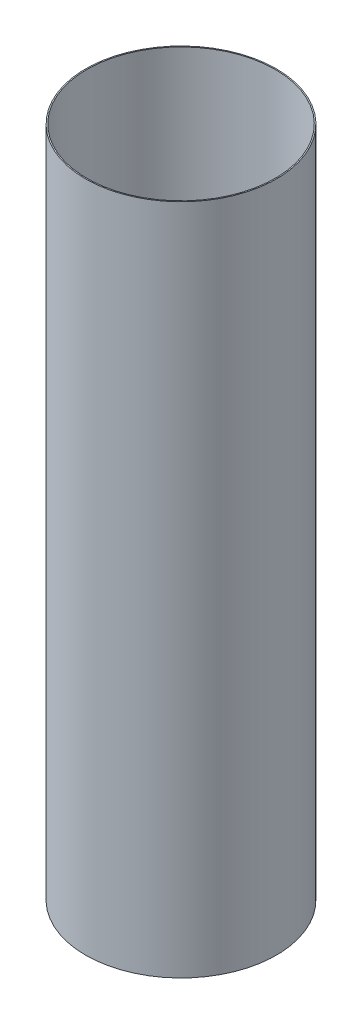
SolidWorks part; units mm, degrees
material "Hexcel AS4C (3000 Filaments)"
ref_plane "Front Plane" through (0, 0, 0) normal (0, 0, 1) x (1, 0, 0)
ref_plane "Top Plane" through (0, 0, 0) normal (0, 1, 0) x (1, 0, 0)
ref_plane "Right Plane" through (0, 0, 0) normal (1, 0, 0) x (0, 0, -1)
sketch "Sketch1" plane through (0, 0, 0) normal (0, 1, 0) x (1, 0, 0)
  circle A0 centre (0, 0) radius 83.439
  circle A1 centre (0, 0) radius 84.455
  dimension "D1" = 168.91
  dimension "D2" = 1.016
extrude "Boss-Extrude1" add sketch "Sketch1" along normal blind 595.0295
ref_plane "Plane1" through (0, 297.5148, 0) normal (0, 1, 0) x (1, 0, 0)
sketch "Sketch2" plane through (0, 0, 0) normal (0, 0, 1) x (1, 0, 0)
  line L0 (0, 3.81) -> (0, -68.0288) construction
  line L1 (3.175, 3.81) -> (3.175, -68.0288)
  line L2 (-3.175, 3.81) -> (-3.175, -68.0288)
  line L3 (-84.455, 0) -> (84.455, 0) construction
  arc A0 (3.175, 3.81) -> (-3.175, 3.81) centre (0, 3.81) ccw
  arc A1 (-3.175, -68.0288) -> (3.175, -68.0288) centre (0, -68.0288) ccw
  point P3 (0, -32.1094)
  dimension "D2" = 6.35
  dimension "D1" = 3.81
extrude "Cut-Extrude1" [suppressed] cut sketch "Sketch2" against normal through all
pattern_circular "CirPattern1" [suppressed] count 12 over 360 of bodies 102
mirror "Mirror1" [suppressed] about plane through (0, 297.5148, 0) normal (0, 1, 0)
equation "\"nominalLength\"= 24in"
equation "\"interfaceOffset\"= 0.36217in - 0.1507 / 2in"
equation "\"sheetLength\"= \"nominalLength\" - 2 * \"interfaceOffset\""
equation "\"D1@Boss-Extrude1\"=\"sheetLength\""
